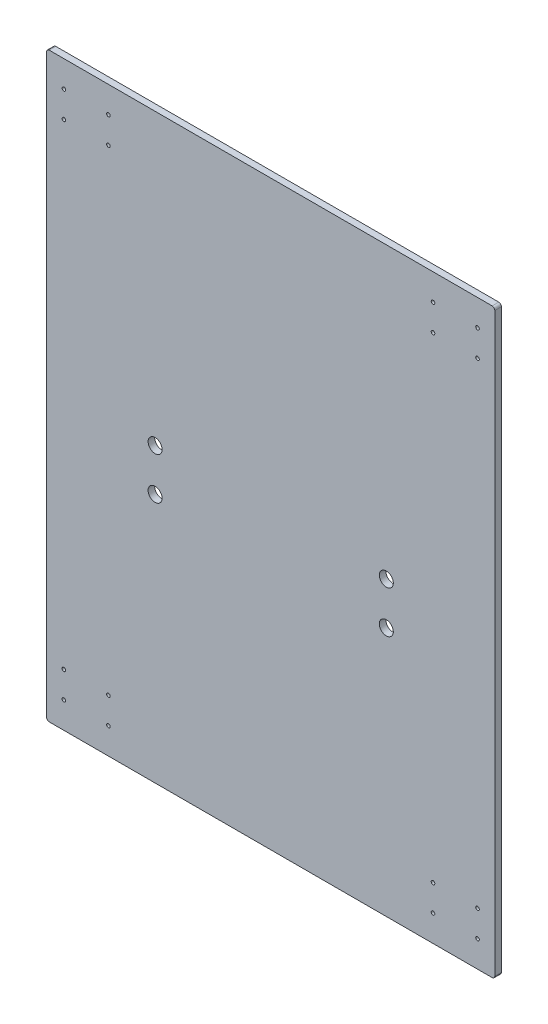
SolidWorks part; units mm, degrees
material "Plain Carbon Steel"
ref_plane "Front Plane" through (0, 0, 0) normal (0, 0, 1) x (1, 0, 0)
ref_plane "Top Plane" through (0, 0, 0) normal (0, 1, 0) x (1, 0, 0)
ref_plane "Right Plane" through (0, 0, 0) normal (1, 0, 0) x (0, 0, -1)
sketch "Sketch1" plane through (0, 0, 0) normal (0, 0, 1) x (1, 0, 0)
  line L1 (0, 0) -> (0, 38.1) construction
  line L2 (393.7, -522.3669) -> (-38.1, -522.3669)
  line L3 (393.7, -522.3669) -> (393.7, 38.1)
  line L4 (393.7, 38.1) -> (-38.1, 38.1)
  line L5 (-38.1, -522.3669) -> (-38.1, 38.1)
  line L6 (393.7, -522.3669) -> (-38.1, 38.1) construction
  line L7 (393.7, 38.1) -> (-38.1, -522.3669) construction
  line L9 (0, 0) -> (-38.1, 0) construction
  line L10 (-25.4, -21.4312) -> (-25.4, 21.4312) construction
  point P4 (177.8, -242.1334)
  dimension "D1" = 12.7
extrude "Boss-Extrude1" add sketch "Sketch1" along normal blind 6.35
fillet "Fillet1" radius 2.54 4 edges at (393.7, 38.1, 3.175) (393.7, -522.3669, 3.175) (-38.1, -522.3669, 3.175) (-38.1, 38.1, 3.175)
sketch "Sketch3" plane through (0, 0, 0) normal (0, 0, -1) x (-1, 0, 0)
  line L0 (-177.8, 38.1) -> (-177.8, -522.3669) construction
  line L1 (-391.16, 38.1) -> (35.56, 38.1) construction
  line L2 (35.56, -522.3669) -> (-391.16, -522.3669) construction
  line L3 (-177.8, -261.1431) -> (-289.1714, -261.1431) construction
  line L4 (-289.1714, -240.8231) -> (-289.1714, -281.4631) construction
  point P8 (-289.1714, -240.8231)
  point P9 (-289.1714, -281.4631)
  point P13 (-66.4286, -281.4631)
  point P14 (-66.4286, -240.8231)
  dimension "D1" = 40.64
  dimension "D2" = 240.9038
  dimension "D3" = 222.7428
hole_wizard "1/2 Clearance Hole1" positions "Sketch3" profile "Sketch4" hole size "1/2" standard "ANSI Inch" end condition up to next
sketch "Sketch4" plane through (66.4286, -240.8231, 0) normal (1, 0, 0) x (0, 1, 0)
  line L0 (0, 0) -> (0, 6.35)
  line L1 (0, 6.35) -> (6.7462, 6.35)
  line L2 (6.7462, 6.35) -> (6.7462, 0)
  line L5 (6.7462, 0) -> (0, 0)
  line L11 (0, -6.35) -> (0, 107.95) construction
  dimension "Thru Hole Dia." = 13.4925
  dimension "Thru Hole Depth" = 6.35
sketch "Sketch6" plane through (0, 0, 0) normal (0, 0, -1) x (-1, 0, 0)
  line L0 (-393.7, -519.8269) -> (-393.7, 35.56) construction
  line L1 (-391.16, 38.1) -> (35.56, 38.1) construction
  line L2 (-177.8, 38.1) -> (-177.8, -522.3669) construction
  line L3 (35.56, -522.3669) -> (-391.16, -522.3669) construction
  line L4 (38.1, -242.1334) -> (-393.7, -242.1334) construction
  line L5 (38.1, 35.56) -> (38.1, -519.8269) construction
  point P0 (-377.0376, 12.7)
  point P1 (-377.0376, -12.7)
  point P2 (-334.1624, 12.7)
  point P3 (-334.1624, -12.7)
  point P16 (-21.4376, -12.7)
  point P17 (21.4376, -12.7)
  point P18 (21.4376, 12.7)
  point P19 (-21.4376, 12.7)
  point P20 (-21.4376, -496.9669)
  point P21 (21.4376, -496.9669)
  point P22 (21.4376, -471.5669)
  point P23 (-21.4376, -471.5669)
  point P24 (-334.1624, -471.5669)
  point P25 (-334.1624, -496.9669)
  point P26 (-377.0376, -471.5669)
  point P27 (-377.0376, -496.9669)
  dimension "D1" = 16.6624
  dimension "D2" = 25.4
  dimension "D3" = 25.4
  dimension "D4" = 42.8752
hole_wizard "#5 Clearance Hole1" positions "Sketch6" profile "Sketch7" hole size "#5" standard "ANSI Inch" end condition up to next
sketch "Sketch7" plane through (377.0376, 12.7, 0) normal (1, 0, 0) x (0, 1, 0)
  line L0 (0, 0) -> (0, 6.35)
  line L1 (0, 6.35) -> (1.7272, 6.35)
  line L2 (1.7272, 6.35) -> (1.7272, 0)
  line L5 (1.7272, 0) -> (0, 0)
  line L11 (0, -6.35) -> (0, 107.95) construction
  dimension "Thru Hole Dia." = 3.4544
  dimension "Thru Hole Depth" = 6.35
